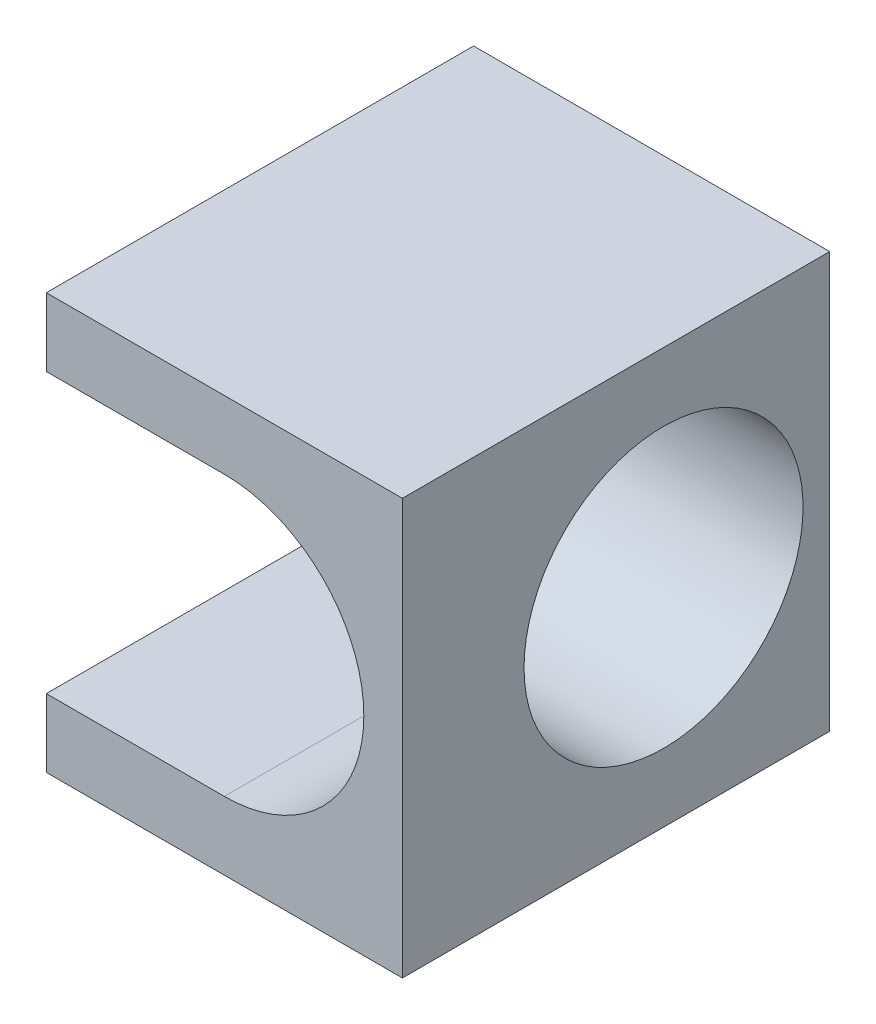
SolidWorks part; units mm, degrees
ref_plane "Front Plane" through (0, 0, 0) normal (0, 0, 1) x (1, 0, 0)
ref_plane "Top Plane" through (0, 0, 0) normal (0, 1, 0) x (1, 0, 0)
ref_plane "Right Plane" through (0, 0, 0) normal (1, 0, 0) x (0, 0, -1)
sketch "Sketch1" plane through (0, 0, 0) normal (0, 1, 0) x (1, 0, 0)
  line L1 (-15, 18) -> (15, 18)
  line L2 (-15, 18) -> (-15, -18)
  line L3 (-15, -18) -> (15, -18)
  line L4 (15, 18) -> (15, -18)
  line L5 (-15, 18) -> (15, -18) construction
  line L6 (-15, -18) -> (15, 18) construction
  point P0 (0, 0)
  dimension "D1" = 36
  dimension "D2" = 30
extrude "Boss-Extrude1" add sketch "Sketch1" along normal blind 35
sketch "Sketch2" plane through (-15, 0, 0) normal (-1, 0, 0) x (0, 0, 1)
  line L1 (16.5, 0) -> (-16.5, 0) construction
  line L3 (18, 35) -> (18, 0) construction
  circle A0 centre (-4, 17.5) radius 11.75
  dimension "D1" = 23.5
  dimension "D2" = 17.5
  dimension "D3" = 22
extrude "Cut-Extrude1" cut sketch "Sketch2" against normal through all
sketch "Sketch3" plane through (0, 0, 18) normal (0, 0, 1) x (1, 0, 0)
  line L0 (0, -19.25) -> (0, 19.25) construction
  line L1 (16.5, 0) -> (-16.5, 0) construction
  line L2 (0, 29.25) -> (-15, 29.25)
  line L3 (0, 5.75) -> (-15, 5.75)
  line L4 (-15, 5.75) -> (-15, 29.25)
  line L5 (-15, 35) -> (15, 35) construction
  line L6 (-15, 35) -> (-15, 0) construction
  arc A0 (0, 5.75) -> (0, 29.25) centre (0, 17.5) ccw
  dimension "D1" = 23.5
  dimension "D2" = 17.5
  dimension "D3" = 5.75
extrude "Cut-Extrude2" cut sketch "Sketch3" against normal blind 22.5
